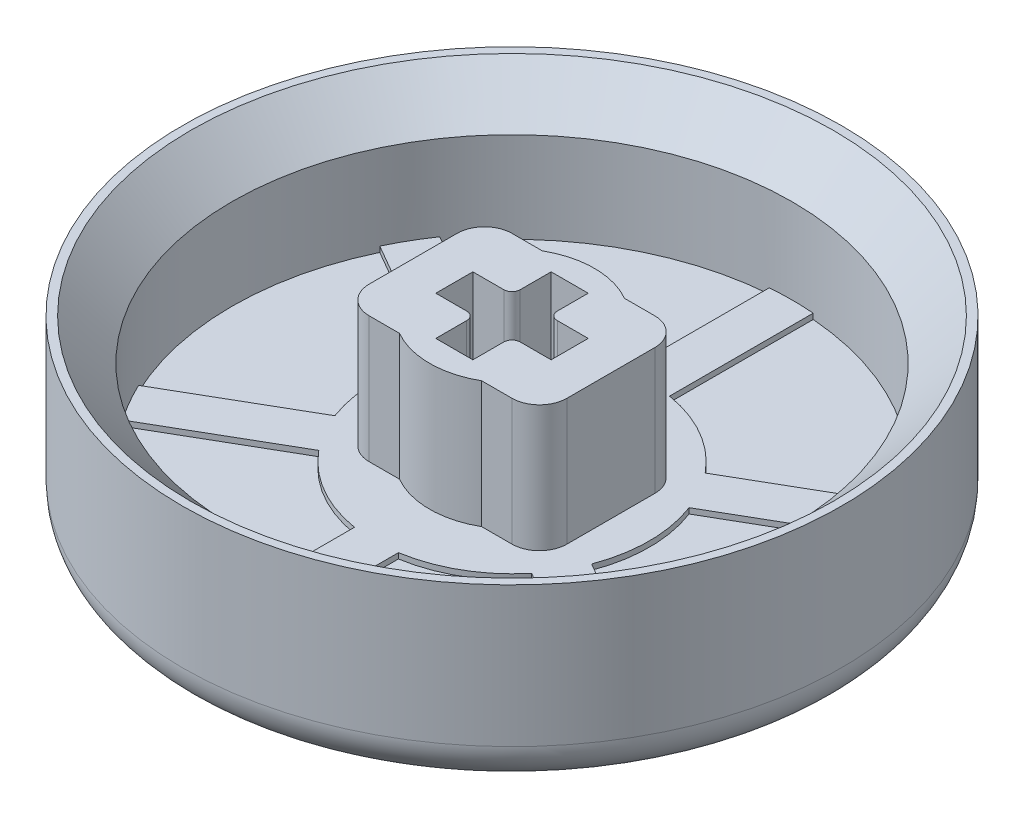
SolidWorks part; units mm, degrees
ref_plane "Front Plane" through (0, 0, 0) normal (0, 0, 1) x (1, 0, 0)
ref_plane "Top Plane" through (0, 0, 0) normal (0, 1, 0) x (1, 0, 0)
ref_plane "Right Plane" through (0, 0, 0) normal (1, 0, 0) x (0, 0, -1)
sketch "Sketch1" plane through (0, 0, 0) normal (0, 1, 0) x (1, 0, 0)
  circle A0 centre (0, 0) radius 12
  dimension "D1" = 24
extrude "button top" add sketch "Sketch1" along normal blind 1.8
sketch "Sketch2" plane through (0, 1.8, 0) normal (0, 1, 0) x (1, 0, 0)
  circle A3 centre (0, 0) radius 12
  circle A4 centre (0, 0) radius 12 construction
  circle A5 centre (0, 0) radius 10.2
  dimension "D1" = 1.8
extrude "button walls" add sketch "Sketch2" along normal blind 4.8
sketch "Sketch5" plane through (0, 1.8, 0) normal (0, 1, 0) x (1, 0, 0)
  circle A0 centre (0, 0) radius 5
  dimension "D1" = 10
extrude "offset" add sketch "Sketch5" along normal blind 0.2
sketch "Sketch3" plane through (0, 1.8, 0) normal (0, 1, 0) x (1, 0, 0)
  line L0 (0, -2.1) -> (0, 2.1) construction
  line L1 (-2.1, 0) -> (2.1, 0) construction
  line L2 (-0.675, 0.975) -> (-0.675, 2.1)
  line L3 (-0.675, -2.1) -> (0.675, -2.1)
  line L4 (-0.675, -2.1) -> (-0.675, -0.975)
  line L5 (-0.675, 2.1) -> (0.675, 2.1)
  line L6 (0.675, -2.1) -> (0.675, -0.975)
  line L7 (-0.675, -2.1) -> (0.675, 2.1) construction
  line L8 (-0.675, 2.1) -> (0.675, -2.1) construction
  line L9 (-2.1, -0.675) -> (-0.975, -0.675)
  line L10 (-2.1, -0.675) -> (-2.1, 0.675)
  line L11 (-2.1, 0.675) -> (-0.975, 0.675)
  line L12 (2.1, -0.675) -> (2.1, 0.675)
  line L13 (-2.1, -0.675) -> (2.1, 0.675) construction
  line L14 (-2.1, 0.675) -> (2.1, -0.675) construction
  line L15 (0.975, 0.675) -> (2.1, 0.675)
  line L16 (0.675, 0.975) -> (0.675, 2.1)
  line L17 (0.975, -0.675) -> (2.1, -0.675)
  line L19 (-3.6, -2.6) -> (3.6, -2.6)
  line L20 (-3.6, -2.6) -> (-3.6, 2.6)
  line L21 (-3.6, 2.6) -> (3.6, 2.6)
  line L22 (3.6, -2.6) -> (3.6, 2.6)
  line L23 (-3.6, -2.6) -> (3.6, 2.6) construction
  line L24 (-3.6, 2.6) -> (3.6, -2.6) construction
  arc A1 (-0.675, -0.975) -> (-0.975, -0.675) centre (-0.975, -0.975) ccw
  arc A2 (0.675, -0.975) -> (0.975, -0.675) centre (0.975, -0.975) cw
  arc A3 (0.975, 0.675) -> (0.675, 0.975) centre (0.975, 0.975) cw
  arc A4 (-0.675, 0.975) -> (-0.975, 0.675) centre (-0.975, 0.975) cw
  circle A5 centre (0, 0) radius 3
  point P0 (0, 0)
  point P6 (0, 0)
  point P9 (0, 0)
  point P22 (2.1, 0)
  point P24 (0, 2.1)
  point P29 (0.675, -0.675)
  point P32 (0.675, 0.675)
  dimension "D1" = 7.2
  dimension "D4" = 0.3
  dimension "D6" = 6
  dimension "D2" = 4.2
  dimension "D3" = 1.35
  dimension "D5" = 5.2
extrude "stem housing" add sketch "Sketch3" along normal blind 4.6 from surface contours A5 L19 L22 L21 | L19 A5 L21 A4 L2 L5 L16 A3 L15 L12 L17 A2 L6 L3 L4 A1 L9 L10 L11 | L19 A5 | A5 L21 L20 L19 | L21 A5 region at (-3.5439, 1.8, 0) region at (-2.9206, 1.8, 0) region at (0, 1.8, 2.761) region at (2.6457, 1.8, 1.5297) region at (0, 1.8, -2.761) starting at face at (0, 2, 5)
sketch "Sketch4" plane through (0, 1.8, 0) normal (0, 1, 0) x (1, 0, 0)
  line L0 (0, 3.9185) -> (0, 10.2) construction
  line L1 (-0.8, 3.9185) -> (-0.8, 10.2)
  line L2 (0.8, 3.9185) -> (0.8, 10.2)
  line L3 (-3.3935, 1.9593) -> (-8.8335, 5.1) construction
  line L4 (-3.7935, 1.2664) -> (-9.2335, 4.4072)
  line L5 (-2.9935, 2.6521) -> (-8.4335, 5.7928)
  line L6 (-3.3935, -1.9593) -> (-8.8335, -5.1) construction
  line L7 (-2.9935, -2.6521) -> (-8.4335, -5.7928)
  line L8 (-3.7935, -1.2664) -> (-9.2335, -4.4072)
  line L9 (0, -3.9185) -> (0, -10.2) construction
  line L10 (0.8, -3.9185) -> (0.8, -10.2)
  line L11 (-0.8, -3.9185) -> (-0.8, -10.2)
  line L12 (3.3935, -1.9593) -> (8.8335, -5.1) construction
  line L13 (3.7935, -1.2664) -> (9.2335, -4.4072)
  line L14 (2.9935, -2.6521) -> (8.4335, -5.7928)
  line L15 (3.3935, 1.9593) -> (8.8335, 5.1) construction
  line L16 (2.9935, 2.6521) -> (8.4335, 5.7928)
  line L17 (3.7935, 1.2664) -> (9.2335, 4.4072)
  circle A2 centre (0, 0) radius 10.2 construction
  arc A3 (-0.8, 3.9185) -> (0.8, 3.9185) centre (0, 3.9185) ccw
  arc A4 (0.8, 10.2) -> (-0.8, 10.2) centre (0, 10.2) ccw
  arc A5 (-3.7935, 1.2664) -> (-2.9935, 2.6521) centre (-3.3935, 1.9593) ccw
  arc A6 (-8.4335, 5.7928) -> (-9.2335, 4.4072) centre (-8.8335, 5.1) ccw
  arc A7 (-2.9935, -2.6521) -> (-3.7935, -1.2664) centre (-3.3935, -1.9593) ccw
  arc A8 (-9.2335, -4.4072) -> (-8.4335, -5.7928) centre (-8.8335, -5.1) ccw
  arc A9 (0.8, -3.9185) -> (-0.8, -3.9185) centre (0, -3.9185) ccw
  arc A10 (-0.8, -10.2) -> (0.8, -10.2) centre (0, -10.2) ccw
  arc A11 (3.7935, -1.2664) -> (2.9935, -2.6521) centre (3.3935, -1.9593) ccw
  arc A12 (8.4335, -5.7928) -> (9.2335, -4.4072) centre (8.8335, -5.1) ccw
  arc A13 (2.9935, 2.6521) -> (3.7935, 1.2664) centre (3.3935, 1.9593) ccw
  arc A14 (9.2335, 4.4072) -> (8.4335, 5.7928) centre (8.8335, 5.1) ccw
  point P9 (0, 7.0593)
  point P18 (-6.1135, 3.5296)
  point P25 (-6.1135, -3.5296)
  point P32 (0, -7.0593)
  point P39 (6.1135, -3.5296)
  point P46 (6.1135, 3.5296)
  point P51 (0, 0)
  dimension "D1" = 1.6
  dimension "D2" = 6
extrude "spokes" add sketch "Sketch4" along normal up to surface (0.2 mm away) up to face at (0, 2, 0)
fillet "Fillet1" radius 1.5 1 edges at (0, 0, 12)
chamfer "Chamfer1" distance 1.5 angle 45 1 edges at (0, 6.6, 10.2)
fillet "Fillet2" radius 1 4 edges at (-3.6, 4.3, -2.6) (3.6, 4.3, -2.6) (-3.6, 4.3, 2.6) (3.6, 4.3, 2.6)
